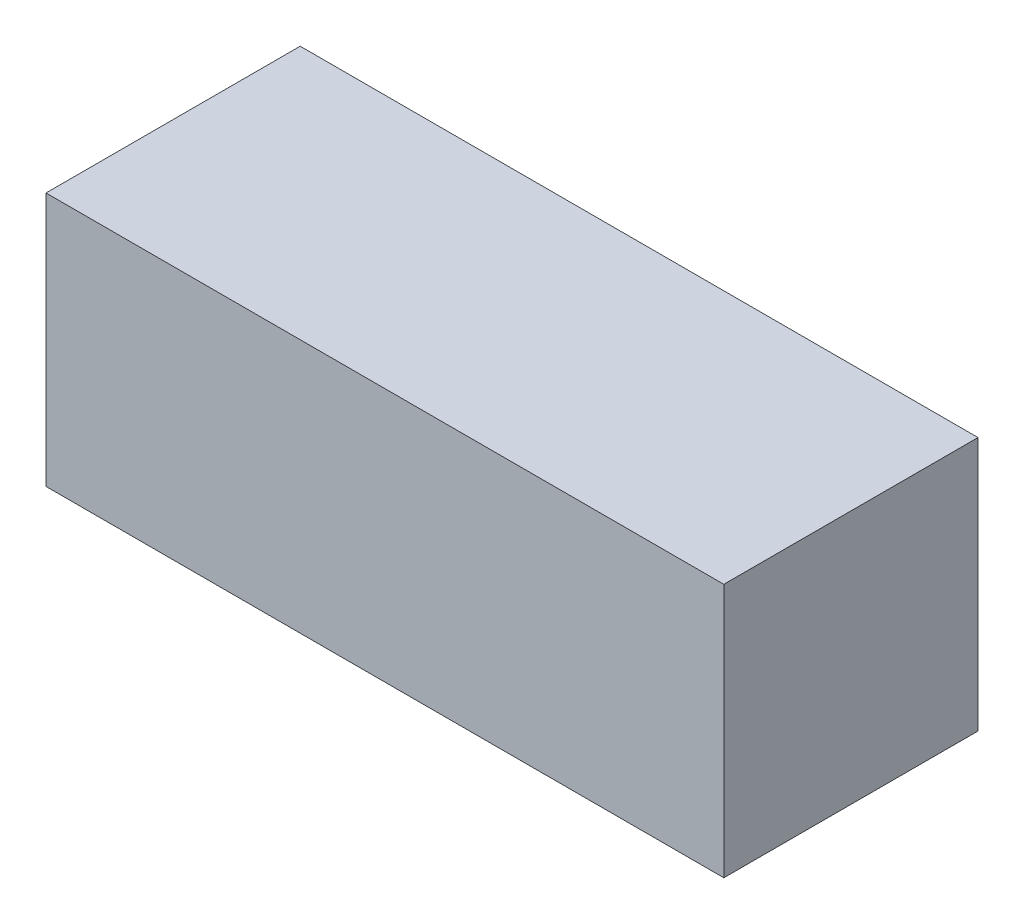
SolidWorks part; units mm, degrees
ref_plane "前视基准面" through (0, 0, 0) normal (0, 0, 1) x (1, 0, 0)
ref_plane "上视基准面" through (0, 0, 0) normal (0, 1, 0) x (1, 0, 0)
ref_plane "右视基准面" through (0, 0, 0) normal (1, 0, 0) x (0, 0, -1)
other "Configuration Table"
sketch "草图1" plane through (0, 0, 0) normal (0, 0, 1) x (1, 0, 0)
  line L1 (-60, -22.5) -> (60, -22.5)
  line L2 (-60, -22.5) -> (-60, 22.5)
  line L3 (-60, 22.5) -> (60, 22.5)
  line L4 (60, -22.5) -> (60, 22.5)
  line L5 (-60, -22.5) -> (60, 22.5) construction
  line L6 (-60, 22.5) -> (60, -22.5) construction
  point P0 (0, 0)
extrude "凸台-拉伸1" add sketch "草图1" along normal blind 45
